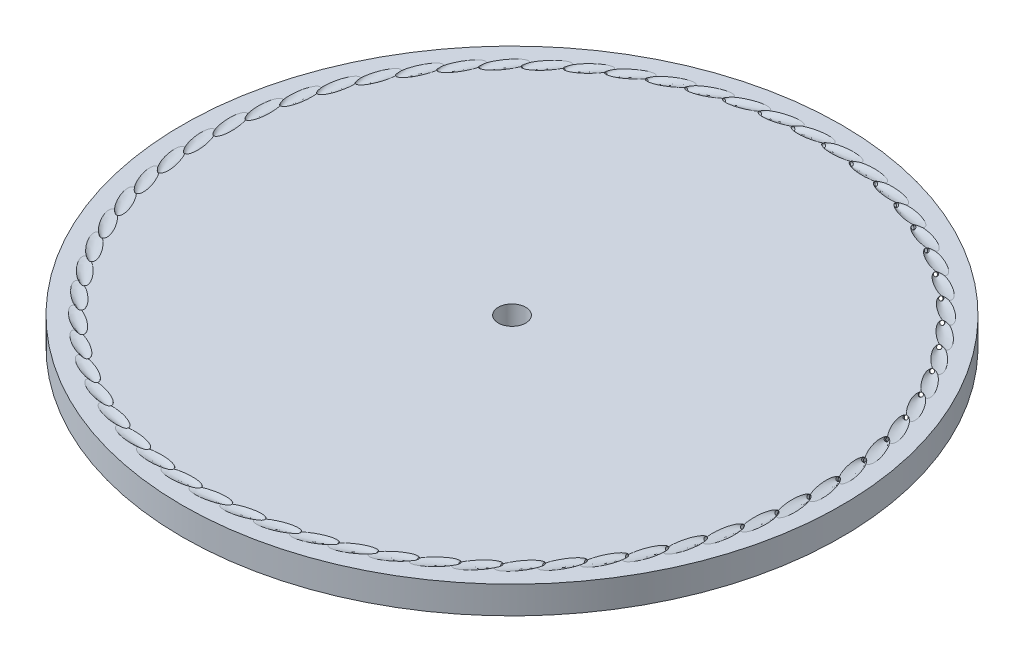
SolidWorks part; units mm, degrees
material "AISI 316 Annealed Stainless Steel Bar (SS)"
ref_plane "Front Plane" through (0, 0, 0) normal (0, 0, 1) x (1, 0, 0)
ref_plane "Top Plane" through (0, 0, 0) normal (0, 1, 0) x (1, 0, 0)
ref_plane "Right Plane" through (0, 0, 0) normal (1, 0, 0) x (0, 0, -1)
sketch "Sketch1" plane through (0, 0, 0) normal (0, 1, 0) x (1, 0, 0)
  circle A0 centre (0, 0) radius 152.4
  circle A1 centre (0, 0) radius 6.35
  dimension "D1" = 304.8
  dimension "D2" = 12.7
extrude "Boss-Extrude1" add sketch "Sketch1" along normal blind 12.7
ref_plane "Plane1" through (0, 0, 139.7) normal (0, 0, 1) x (1, 0, 0)
sketch "Sketch2" plane through (0, 0, 139.7) normal (0, 0, 1) x (1, 0, 0)
  line L0 (11.4329, -8.0054) -> (-28.4934, 19.9513)
  line L1 (152.4, 12.7) -> (-152.4, 12.7) construction
  line L2 (-152.4, 0) -> (152.4, 0) construction
  line L4 (-16.6533, 12.7) -> (-15.3529, 11.7894)
  line L5 (-15.3529, 11.7894) -> (17.0383, 0)
  line L6 (5.8275, -16.0108) -> (-16.3295, 10.3948)
  line L7 (-16.3295, 10.3948) -> (-17.6299, 11.3053)
  line L8 (-17.6299, 11.3053) -> (-33.5709, 12.7)
  line L9 (-17.6299, 11.3053) -> (-16.6533, 12.7) construction
  line L12 (-16.6533, 12.7) -> (-23.416, 27.2026)
  line L13 (-23.416, 27.2026) -> (-33.5709, 12.7)
  line L14 (17.0383, 0) -> (5.8275, -16.0108)
  line L15 (0, 0) -> (0, 12.7) construction
  point P14 (-17.1416, 12.0027)
  point P16 (-28.4934, 19.9513)
  point P19 (11.4329, -8.0054)
  dimension "D1" = 55
  dimension "D2" = 1.7026
  dimension "D3" = 15
  dimension "D4" = 15
  dimension "D5" = 1.5875
  dimension "D7" = 30
revolve "Cut-Revolve8" cut sketch "Sketch2" angle 360 about L0 region at (-7.4307, 1.3196, 139.7)
pattern_circular "CirPattern1" count 64 over 360 about axis through (0, 12.7, 0) along (0, -1, 0) of "Cut-Revolve8" reverse direction yes
